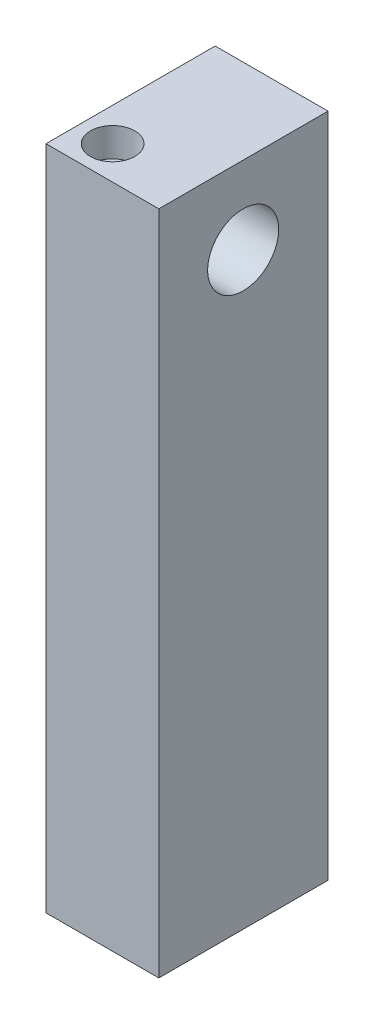
SolidWorks part; units mm, degrees
ref_plane "Front Plane" through (0, 0, 0) normal (0, 0, 1) x (1, 0, 0)
ref_plane "Top Plane" through (0, 0, 0) normal (0, 1, 0) x (1, 0, 0)
ref_plane "Right Plane" through (0, 0, 0) normal (1, 0, 0) x (0, 0, -1)
sketch "Sketch1" plane through (0, 0, 0) normal (0, 1, 0) x (1, 0, 0)
  line L1 (0, 0) -> (50.8, 0)
  line L2 (0, 0) -> (0, 76.2)
  line L3 (0, 76.2) -> (50.8, 76.2)
  line L4 (50.8, 0) -> (50.8, 76.2)
  dimension "D1" = 50.8
  dimension "D2" = 76.2
extrude "Boss-Extrude1" add sketch "Sketch1" along normal blind 300
sketch "Sketch2" plane through (50.8, 0, 0) normal (1, 0, 0) x (0, 0, -1)
  line L1 (0, 0) -> (38, 0)
  line L2 (0, 0) -> (0, 265)
  line L3 (0, 265) -> (38, 265)
  line L4 (38, 0) -> (38, 265)
  circle A0 centre (38, 265) radius 16
  dimension "D1" = 38
  dimension "D2" = 265
extrude "Cut-Extrude1" cut sketch "Sketch2" against normal blind 150 contours L4 A0 L3 | L3 A0 L4 region at (50.8, 258.2094, -31.2094) region at (50.8, 267.2635, -40.2635)
sketch "Sketch4" plane through (0, 300, 0) normal (0, 1, 0) x (1, 0, 0)
  line L5 (50.8, 0) -> (15, 0)
  line L6 (50.8, 0) -> (50.8, 15)
  line L7 (50.8, 15) -> (15, 15)
  line L8 (15, 0) -> (15, 15)
  circle A0 centre (15, 15) radius 5.25
  dimension "D1" = 35.8
  dimension "D2" = 15
extrude "Cut-Extrude3" cut sketch "Sketch4" against normal blind 60 contours A0
sketch "Sketch6" plane through (0, 300, 0) normal (0, 1, 0) x (1, 0, 0)
  circle A1 centre (15, 15) radius 10
extrude "Cut-Extrude4" cut sketch "Sketch6" against normal blind 13
